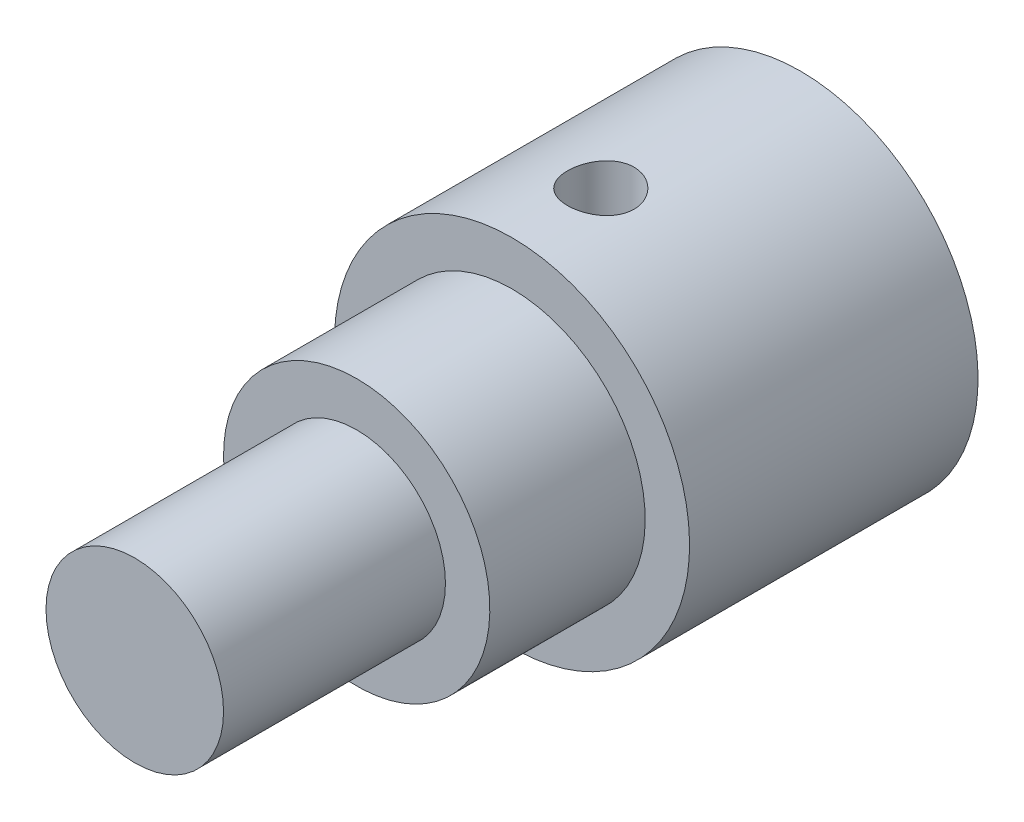
SolidWorks part; units mm, degrees
material "1060 Alloy"
ref_plane "Front Plane" through (0, 0, 0) normal (0, 0, 1) x (1, 0, 0)
ref_plane "Top Plane" through (0, 0, 0) normal (0, 1, 0) x (1, 0, 0)
ref_plane "Right Plane" through (0, 0, 0) normal (1, 0, 0) x (0, 0, -1)
sketch "Sketch1" plane through (0, 0, 0) normal (1, 0, 0) x (0, 0, -1)
  line L0 (0, 0) -> (0, 4)
  line L1 (0, 4) -> (10, 4)
  line L2 (10, 4) -> (10, 6)
  line L3 (10, 6) -> (17, 6)
  line L4 (17, 6) -> (17, 8)
  line L5 (17, 8) -> (30, 8)
  line L6 (17.5772, 0) -> (19.5, 3.2)
  line L7 (17.5772, 0) -> (0, 0)
  line L8 (19.5, 3.2) -> (30, 3.2)
  line L9 (30, 3.2) -> (30, 8)
  dimension "D1" = 4
  dimension "D2" = 10
  dimension "D3" = 7
  dimension "D4" = 6
  dimension "D5" = 13
  dimension "D6" = 8
  dimension "D7" = 3.2
  dimension "D8" = 2.5
  dimension "D9" = 121
revolve "Revolve1" add sketch "Sketch1" angle 360 about L7
sketch "Sketch2" plane through (0, 0, 0) normal (0, 1, 0) x (1, 0, 0)
  line L1 (-8, 17) -> (8, 17) construction
  circle A0 centre (0, 21) radius 1.5
  dimension "D2" = 3
  dimension "D1" = 4
extrude "Cut-Extrude1" cut sketch "Sketch2" against normal up to next and the other way up to next
